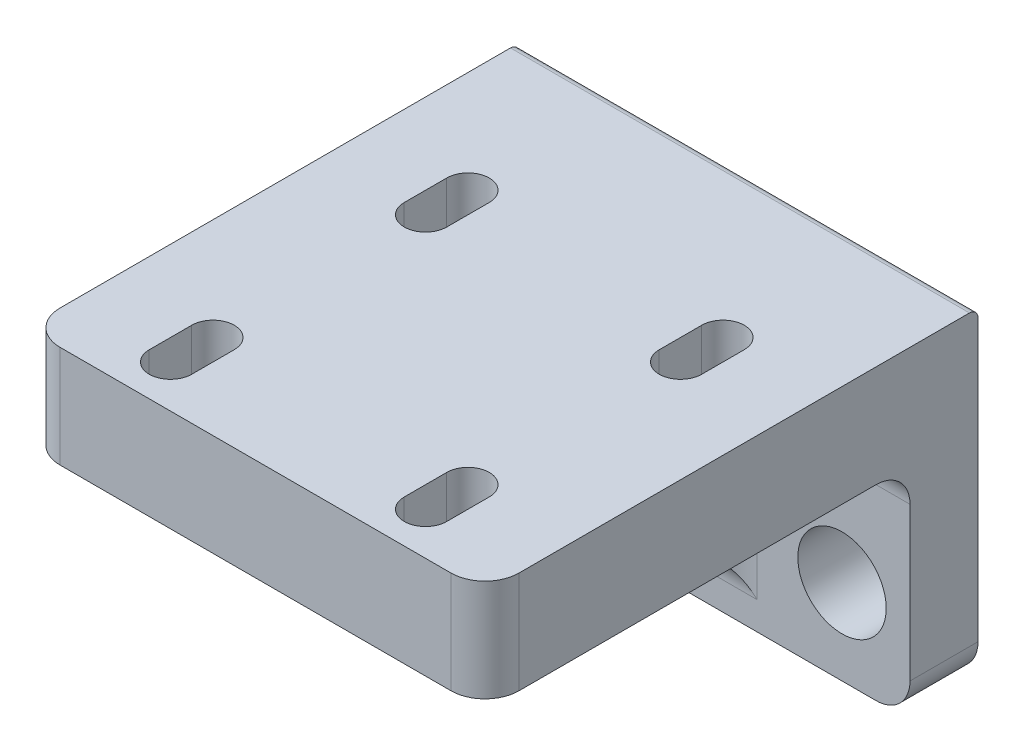
SolidWorks part; units mm, degrees
ref_plane "前视基准面" through (0, 0, 0) normal (0, 0, 1) x (1, 0, 0)
ref_plane "上视基准面" through (0, 0, 0) normal (0, 1, 0) x (1, 0, 0)
ref_plane "右视基准面" through (0, 0, 0) normal (1, 0, 0) x (0, 0, -1)
sketch "草图1" plane through (0, 0, 0) normal (0, 0, 1) x (1, 0, 0)
  line L1 (0, 0) -> (27, 0)
  line L2 (0, 0) -> (0, -16)
  line L3 (0, -16) -> (27, -16)
  line L4 (27, 0) -> (27, -16)
  dimension "D1" = 16
  dimension "D2" = 2
  dimension "D3" = 27
extrude "凸台-拉伸2" add sketch "草图1" along normal blind 3 and the other way blind 1 contours L2 L1 L4 L3
sketch "草图3" plane through (0, 0, 0) normal (0, 1, 0) x (1, 0, 0)
  line L0 (27, -3) -> (27, 1) construction
  line L1 (0, 0) -> (27, 0)
  line L2 (0, 0) -> (0, -28)
  line L3 (0, -28) -> (27, -28)
  line L4 (27, 0) -> (27, -28)
  dimension "D1" = 28
extrude "凸台-拉伸4" add sketch "草图3" against normal blind 3 and the other way blind 3
sketch "草图4" plane through (0, -3, 0) normal (0, -1, 0) x (-1, 0, 0)
  line L0 (-6, -10.5) -> (-6, -8) construction
  line L1 (-7.25, -10.5) -> (-7.25, -8)
  line L2 (-4.75, -10.5) -> (-4.75, -8)
  line L3 (-21, -10.5) -> (-21, -8) construction
  line L4 (-22.25, -10.5) -> (-22.25, -8)
  line L5 (-19.75, -10.5) -> (-19.75, -8)
  line L6 (-6, -25.5) -> (-6, -23) construction
  line L7 (-7.25, -25.5) -> (-7.25, -23)
  line L8 (-4.75, -25.5) -> (-4.75, -23)
  line L9 (-21, -25.5) -> (-21, -23) construction
  line L10 (-22.25, -25.5) -> (-22.25, -23)
  line L11 (-19.75, -25.5) -> (-19.75, -23)
  line L12 (0, -3) -> (0, -28) construction
  line L13 (-27, -28) -> (-27, -3) construction
  arc A0 (-7.25, -10.5) -> (-4.75, -10.5) centre (-6, -10.5) ccw
  arc A1 (-4.75, -8) -> (-7.25, -8) centre (-6, -8) ccw
  arc A2 (-22.25, -10.5) -> (-19.75, -10.5) centre (-21, -10.5) ccw
  arc A3 (-19.75, -8) -> (-22.25, -8) centre (-21, -8) ccw
  arc A4 (-7.25, -25.5) -> (-4.75, -25.5) centre (-6, -25.5) ccw
  arc A5 (-4.75, -23) -> (-7.25, -23) centre (-6, -23) ccw
  arc A6 (-22.25, -25.5) -> (-19.75, -25.5) centre (-21, -25.5) ccw
  arc A7 (-19.75, -23) -> (-22.25, -23) centre (-21, -23) ccw
  point P2 (-6, -9.25)
  point P11 (-21, -9.25)
  point P18 (-6, -24.25)
  point P25 (-21, -24.25)
  dimension "D1" = 2
  dimension "D3" = 25
  dimension "D4" = 4.75
  dimension "D5" = 12.5
  dimension "D2" = 2
extrude "切除-拉伸11" cut sketch "草图4" against normal blind 13
sketch "草图8" plane through (0, -3, 0) normal (0, -1, 0) x (-1, 0, 0)
  line L0 (0, -28) -> (-27, -28) construction
  point P0 (-13.5, -28)
sketch "草图9" plane through (0, 0, 3) normal (0, 0, 1) x (1, 0, 0)
  line L0 (0, -16) -> (27, -16) construction
  point P0 (13.5, -16)
sketch "草图12" plane through (0, 0, 3) normal (0, 0, 1) x (1, 0, 0)
  point P0 (13.5, -3)
ref_plane "基准面4" through (13.5, 0, 0) normal (-1, 0, 0) x (0, 0, 1)
sketch "草图13" plane through (13.5, 0, 0) normal (-1, 0, 0) x (0, 0, 1)
  line L0 (3, -13) -> (28, -3)
  line L2 (3, -13) -> (3, -3)
  line L3 (3, -3) -> (28, -3)
extrude "凸台-拉伸5" add sketch "草图13" against normal blind 2.5 and the other way blind 2.5
fillet "圆角2" radius 2 6 edges at (5.5, -3, 3) (21.5, -3, 3) (0, -16, 1) (27, -16, 1) (27, 0, 28) (0, 0, 28)
fillet "圆角3" radius 2 7 edges at (13.5, -13, 3) (16, -3, 16.5) (16, -3.5858, 3.5858) (16, -9, 3) (11, -9, 3) (11, -3, 16.5) (11, -3.5858, 3.5858)
sketch "草图14" plane through (0, 0, 0) normal (0, 0, -1) x (-1, 0, 0)
  line L1 (-27, 3) -> (0, 3)
  line L2 (-27, 3) -> (-27, 0)
  line L3 (-27, 0) -> (0, 0)
  line L4 (0, 3) -> (0, 0)
extrude "凸台-拉伸6" add sketch "草图14" along normal blind 1
fillet "圆角5" radius 0.5 1 edges at (13.5, 3, -1)
sketch "草图16" plane through (0, 0, 3) normal (0, 0, 1) x (1, 0, 0)
  line L0 (0, -5) -> (0, -14) construction
  line L1 (9, -5) -> (0, -5) construction
  line L2 (27, -5) -> (27, -14) construction
  line L3 (27, -5) -> (18, -5) construction
  circle A0 centre (4, -11) radius 2.6
  circle A3 centre (23, -11) radius 2.6
  dimension "D1" = 4
  dimension "D2" = 6
  dimension "D5" = 4
  dimension "D8" = 6
extrude "切除-拉伸12" cut sketch "草图16" against normal blind 4
